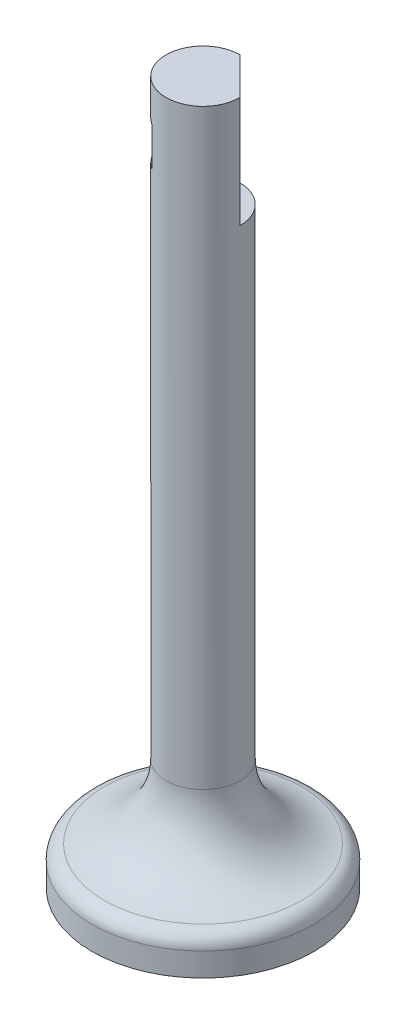
SolidWorks part; units mm, degrees
ref_plane "Спереди" through (0, 0, 0) normal (0, 0, 1) x (1, 0, 0)
ref_plane "Сверху" through (0, 0, 0) normal (0, 1, 0) x (1, 0, 0)
ref_plane "Справа" through (0, 0, 0) normal (1, 0, 0) x (0, 0, -1)
sketch "Sketch1" plane through (0, 0, 0) normal (0, 1, 0) x (1, 0, 0)
  circle A0 centre (0, 0) radius 15
  dimension "D1" = 30
extrude "Boss-Extrude1" add sketch "Sketch1" along normal blind 5
sketch "Sketch2" plane through (0, 5, 0) normal (0, 1, 0) x (1, 0, 0)
  circle A0 centre (0, 0) radius 5
  dimension "D1" = 10
extrude "Boss-Extrude2" add sketch "Sketch2" along normal blind 90
sketch "Sketch3" plane through (0, 95, 0) normal (0, 1, 0) x (1, 0, 0)
  line L0 (0, 5) -> (5, 0)
  circle A0 centre (0, 0) radius 5 construction
  arc A1 (0, 5) -> (5, 0) centre (0, 0) cw
extrude "Cut-Extrude1" cut sketch "Sketch3" against normal blind 15
sketch "Sketch4" plane through (2.5, 0, -2.5) normal (0.7071, 0, -0.7071) x (-0.7071, 0, -0.7071)
  line L0 (0, 95) -> (0, 80) construction
  line L1 (3.5355, 95) -> (-3.5355, 95) construction
  line L2 (3.5355, 80) -> (-3.5355, 80) construction
  line L4 (1, 90.1) -> (-1, 90.1)
  line L5 (1, 90.1) -> (1, 84.9)
  line L6 (1, 84.9) -> (-1, 84.9)
  line L7 (-1, 90.1) -> (-1, 84.9)
  line L8 (1, 90.1) -> (-1, 84.9) construction
  line L9 (1, 84.9) -> (-1, 90.1) construction
  point P6 (0, 87.5)
  dimension "D1" = 5.2
  dimension "D2" = 2
extrude "Cut-Extrude2" cut sketch "Sketch4" against normal through all
fillet "Fillet1" radius 10 1 edges at (0, 5, 5)
fillet "Fillet2" radius 2 1 edges at (0, 5, 15)
sketch "Sketch5" plane through (0, 0, 0) normal (0, -1, 0) x (1, 0, 0)
  line L0 (10.6066, -10.6066) -> (-10.6066, 10.6066) construction
  line L1 (3.3153, 14.629) -> (-14.629, -3.3153) construction
  line L2 (0, -5) -> (5, 0) construction
  circle A0 centre (0, 0) radius 15 construction
  text T0 "M" font "Arial" height 15
  point P2 (-5.6569, 5.6569)
  dimension "D1" = 7
extrude "Cut-Extrude3" cut sketch "Sketch5" against normal blind 1
sketch "Sketch6" plane through (0, 0, 0) normal (0, -1, 0) x (1, 0, 0)
  circle A0 centre (0, 0) radius 11.5
  circle A1 centre (0, 0) radius 13.5
  dimension "D1" = 2
  dimension "D2" = 27
extrude "Cut-Extrude4" cut sketch "Sketch6" against normal blind 1
